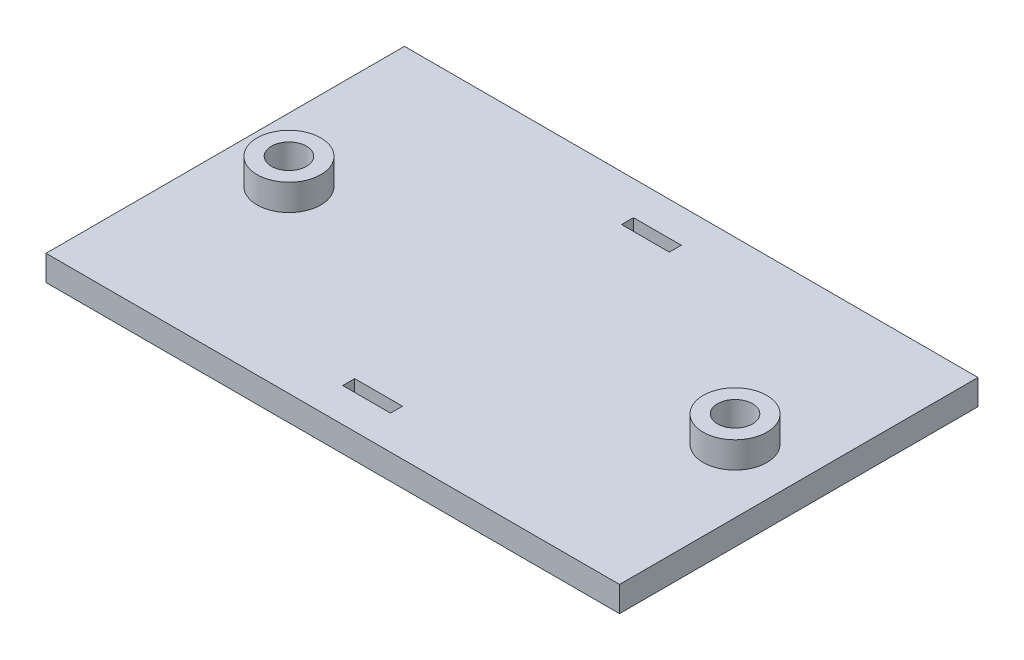
SolidWorks part; units mm, degrees
ref_plane "Front Plane" through (0, 0, 0) normal (0, 0, 1) x (1, 0, 0)
ref_plane "Top Plane" through (0, 0, 0) normal (0, 1, 0) x (1, 0, 0)
ref_plane "Right Plane" through (0, 0, 0) normal (1, 0, 0) x (0, 0, -1)
sketch "Plate Sketch" plane through (0, 0, 0) normal (0, 1, 0) x (1, 0, 0)
  line L0 (-36, 22.5) -> (36, 22.5)
  line L1 (36, 22.5) -> (36, -22.5)
  line L2 (36, -22.5) -> (-36, -22.5)
  line L3 (-36, -22.5) -> (-36, 22.5)
  line L4 (-3, 18.25) -> (3, 18.25)
  line L5 (3, 18.25) -> (3, 16.75)
  line L6 (3, 16.75) -> (-3, 16.75)
  line L7 (-3, 16.75) -> (-3, 18.25)
  line L8 (-3, -16.75) -> (3, -16.75)
  line L9 (3, -16.75) -> (3, -18.25)
  line L10 (3, -18.25) -> (-3, -18.25)
  line L11 (-3, -18.25) -> (-3, -16.75)
  circle A0 centre (-28, 0) radius 2.2
  circle A1 centre (28, 0) radius 2.2
extrude "Plate" add sketch "Plate Sketch" along normal blind 3.18 from offset 92.57
ref_axis "Engine Axis" through (39.6, 0, 0) along (-1, 0, 0)
sketch "Pads Sketch" plane through (0, 0, 0) normal (0, 1, 0) x (1, 0, 0)
  circle A0 centre (-28, 0) radius 4
  circle A1 centre (28, 0) radius 4
  circle A2 centre (-28, 0) radius 2.2
  circle A3 centre (28, 0) radius 2.2
extrude "Pads" add sketch "Pads Sketch" along normal blind 3.3 from offset 95.75
